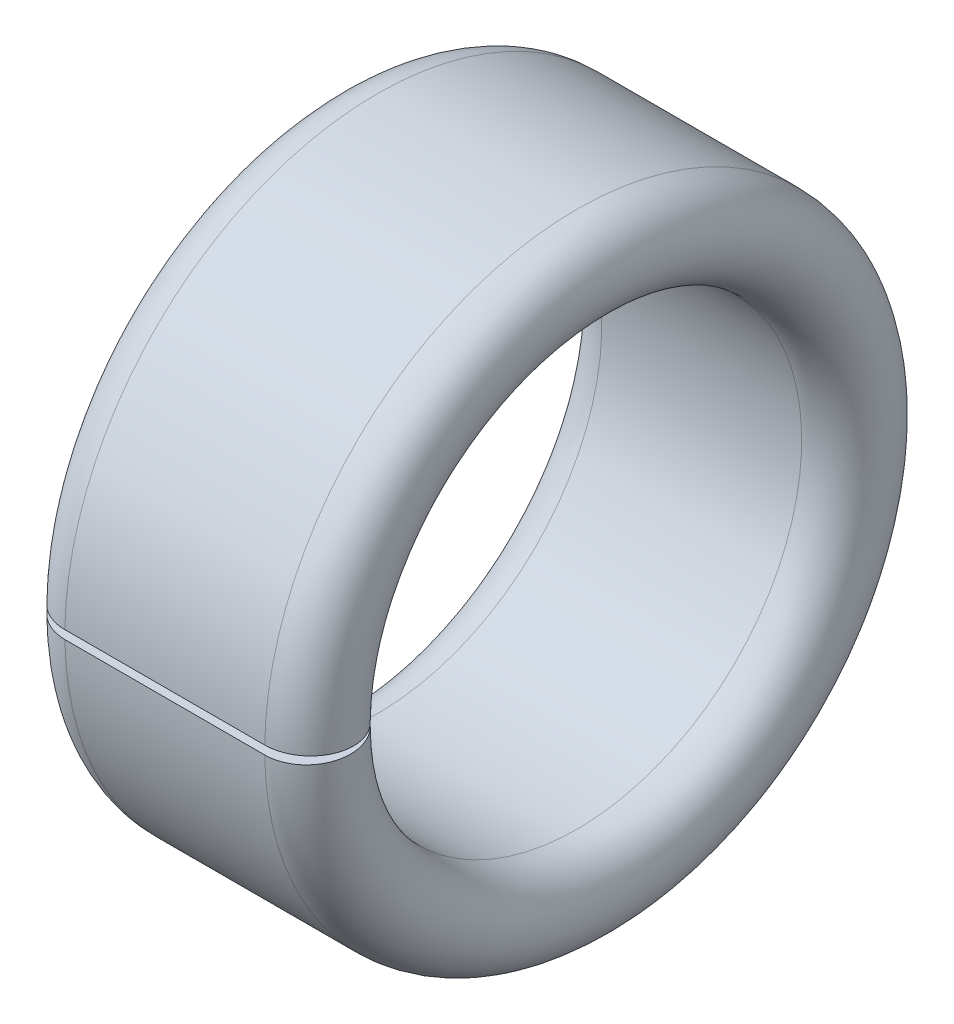
SolidWorks part; units mm, degrees
ref_plane "Front Plane" through (0, 0, 0) normal (0, 0, 1) x (1, 0, 0)
ref_plane "Top Plane" through (0, 0, 0) normal (0, 1, 0) x (1, 0, 0)
ref_plane "Right Plane" through (0, 0, 0) normal (1, 0, 0) x (0, 0, -1)
sketch "Sketch1" plane through (0, 0, 0) normal (0, 0, 1) x (1, 0, 0)
  line L0 (0.35, 1.8) -> (1.95, 1.8)
  line L1 (1.95, 2.5) -> (0.35, 2.5)
  line L2 (2.3, 0) -> (0, 0) construction
  arc A0 (0.35, 2.5) -> (0.35, 1.8) centre (0.35, 2.15) ccw
  arc A1 (1.95, 1.8) -> (1.95, 2.5) centre (1.95, 2.15) ccw
revolve "Revolve1" add sketch "Sketch1" angle 360 about L2
ref_plane "Plane1" through (2.3, 0, 0) normal (1, 0, 0) x (0, 0, -1)
sketch "Sketch2" plane through (0, 0, 0) normal (1, 0, 0) x (0, 0, -1)
  line L0 (-3.4993, -0.0693) -> (-1.5136, 0)
  line L1 (-1.5136, 0) -> (-3.4993, 0.0693)
  arc A0 (-3.4993, 0.0693) -> (-3.4993, -0.0693) centre (0, 0) ccw
extrude "Cut-Extrude1" cut sketch "Sketch2" along normal blind 2.3
ref_plane "ANBAU XY" through (0, 0, 0) normal (1, 0, 0) x (0, 0, -1)
ref_plane "ANBAU XZ" through (0, 0, 0) normal (0, -1, 0) x (-1, 0, 0)
ref_plane "ANBAU YZ" through (0, 0, 0) normal (0, 0, -1) x (-1, 0, 0)
ref_axis "ANBAU X" through (0, 0, 80.9) along (0, 0, -1)
ref_axis "ANBAU Y" through (0, -50, 0) along (0, 1, 0)
ref_axis "ANBAU Z" through (80.9, 0, 0) along (-1, 0, 0)
sketch3d "ANBAU"
  point P0 (0, 0, 0)
ref_plane "insert XY" through (0, 0, 0) normal (1, 0, 0) x (0, 0, -1)
ref_plane "insert XZ" through (0, 0, 0) normal (0, -1, 0) x (-1, 0, 0)
ref_plane "insert YZ" through (0, 0, 0) normal (0, 0, -1) x (-1, 0, 0)
ref_axis "insert X" through (0, 0, 80.9) along (0, 0, -1)
ref_axis "insert Y" through (0, -50, 0) along (0, 1, 0)
ref_axis "insert Z" through (80.9, 0, 0) along (-1, 0, 0)
sketch3d "insert"
  point P0 (0, 0, 0)
ref_plane "schraube_punkt XY" through (2.3, 0, 0) normal (1, 0, 0) x (0, 0, -1)
ref_plane "schraube_punkt XZ" through (0, 0, 0) normal (0, -1, 0) x (-1, 0, 0)
ref_plane "schraube_punkt YZ" through (0, 0, 0) normal (0, 0, -1) x (-1, 0, 0)
ref_axis "schraube_punkt X" through (2.3, 0, 80.9) along (0, 0, -1)
ref_axis "schraube_punkt Y" through (2.3, -50, 0) along (0, 1, 0)
ref_axis "schraube_punkt Z" through (80.9, 0, 0) along (-1, 0, 0)
sketch3d "schraube_punkt"
  point P0 (2.3, 0, 0)
other "Freeze***"
